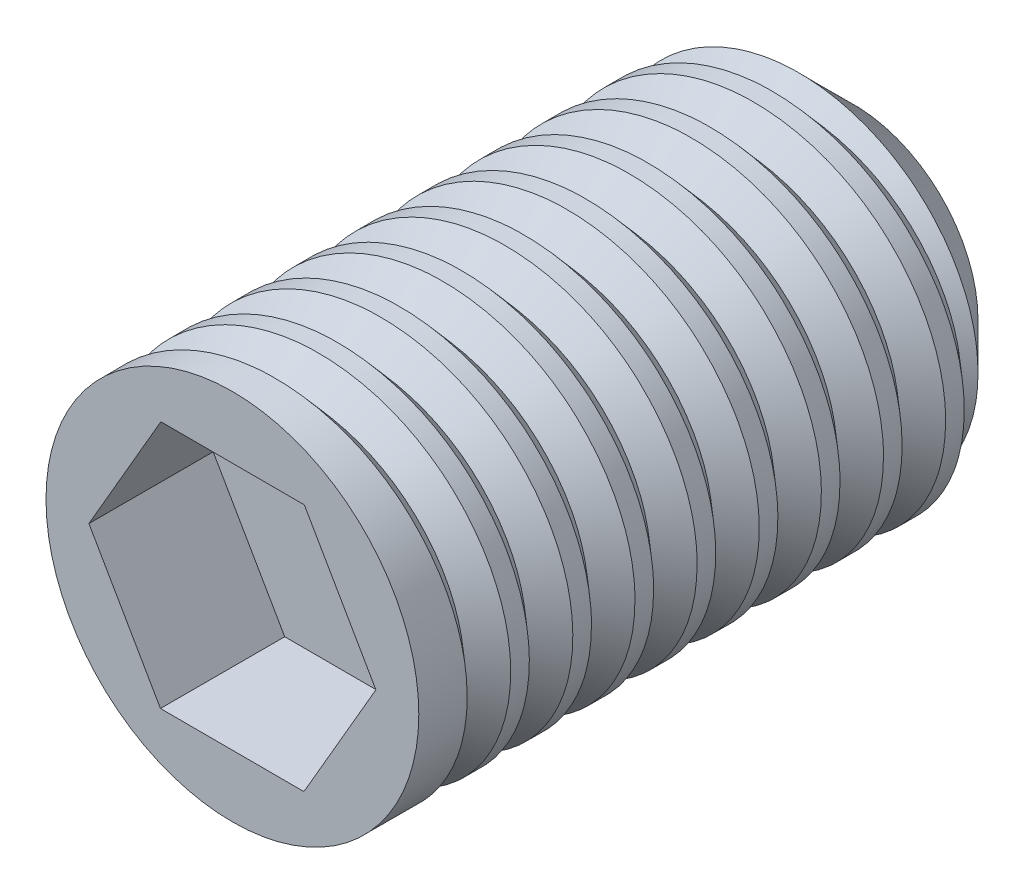
SolidWorks part; units mm, degrees
ref_plane "前视基准面" through (0, 0, 0) normal (0, 0, 1) x (1, 0, 0)
ref_plane "上视基准面" through (0, 0, 0) normal (0, 1, 0) x (1, 0, 0)
ref_plane "右视基准面" through (0, 0, 0) normal (1, 0, 0) x (0, 0, -1)
sketch "草图1" plane through (0, 0, 0) normal (0, 0, 1) x (1, 0, 0)
  circle A0 centre (0, 0) radius 3
  dimension "D1" = 6
extrude "凸台-拉伸1" add sketch "草图1" along normal blind 10
sketch "草图2" plane through (0, 0, 10) normal (0, 0, 1) x (1, 0, 0)
  line L1 (1.158, 1.9981) -> (-1.1514, 2.0019)
  line L2 (-1.1514, 2.0019) -> (-2.3094, 0.0039)
  line L3 (-2.3094, 0.0039) -> (-1.158, -1.9981)
  line L4 (-1.158, -1.9981) -> (1.1514, -2.0019)
  line L5 (1.1514, -2.0019) -> (2.3094, -0.0039)
  line L6 (2.3094, -0.0039) -> (1.158, 1.9981)
  circle A0 centre (0, 0) radius 2 construction
  dimension "D1" = 4
extrude "切除-拉伸1" cut sketch "草图2" against normal blind 2
chamfer "倒角1" distance 1 angle 45 1 edges at (3, 0, 0)
sketch "草图3" plane through (0, 0, 0) normal (0, 0, -1) x (-1, 0, 0)
  circle A0 centre (0, 0) radius 3
curve "螺旋线/涡状线1" pitch 1 height 9.5 radius 3 centre (0, 0, 0) axis (0, 0, 1) start towards (0.7071, 0.7071, 0)
sketch "草图4" plane through (0, 0, 0) normal (1, 0, 0) x (0, 0, -1)
  line L0 (-0.475, 3) -> (0.225, 3)
  line L1 (-0.125, 3) -> (-0.125, 2.6) construction
  line L2 (0.225, 3) -> (-0.125, 2.6)
  line L3 (-0.125, 2.6) -> (-0.475, 3)
  dimension "D1" = 0.7
  dimension "D2" = 0.4
sweep "切除-扫描1" cut profiles "草图4" path "螺旋线/涡状线1" align with end faces yes
